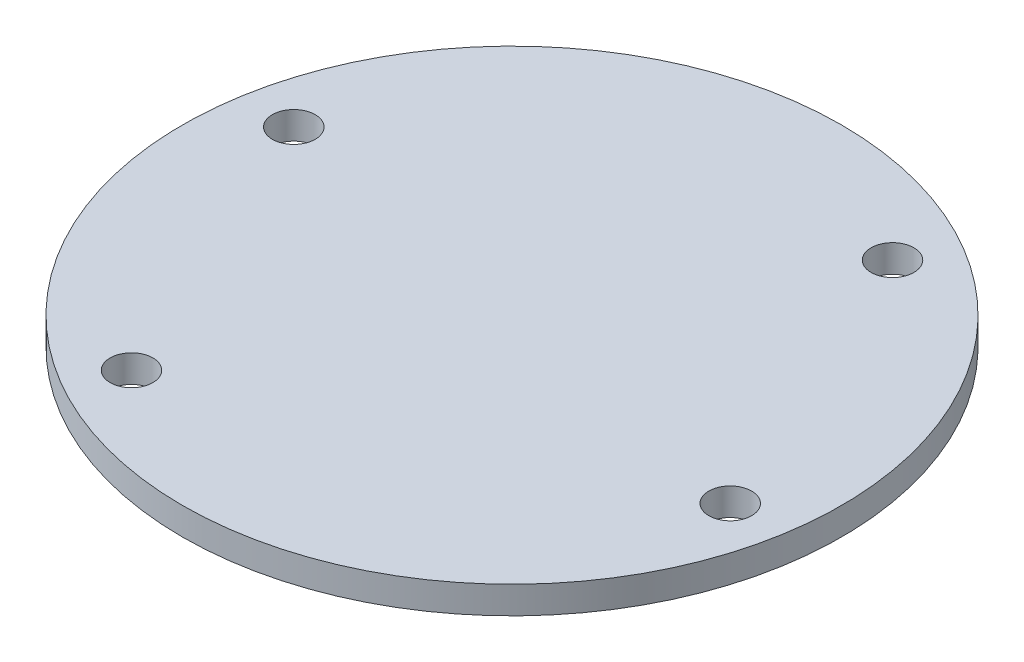
SolidWorks part; units mm, degrees
ref_plane "Front Plane" through (0, 0, 0) normal (0, 0, 1) x (1, 0, 0)
ref_plane "Top Plane" through (0, 0, 0) normal (0, 1, 0) x (1, 0, 0)
ref_plane "Right Plane" through (0, 0, 0) normal (1, 0, 0) x (0, 0, -1)
sketch "Sketch1" plane through (0, 0, 0) normal (0, 1, 0) x (1, 0, 0)
  circle A0 centre (0, 0) radius 19.25
  dimension "D1" = 38.5
extrude "Boss-Extrude1" add sketch "Sketch1" along normal blind 1.6
sketch "Sketch3" plane through (0, 1.6, 0) normal (0, 1, 0) x (1, 0, 0)
  circle A9 centre (-15.8938, 3.1472) radius 1.25
  circle A10 centre (8.3271, 13.8988) radius 1.25
  circle A11 centre (15.8938, -3.1472) radius 1.25
  circle A12 centre (-8.3271, -13.8988) radius 1.25
  point P8 (0, 0)
extrude "Cut-Extrude1" cut sketch "Sketch3" against normal through all contours A9 | A12 | A11 | A10 region at (-15.8938, 1.6, -3.1472) region at (8.3271, 1.6, -13.8988) region at (15.8938, 1.6, 3.1472) region at (-8.3271, 1.6, 13.8988)
